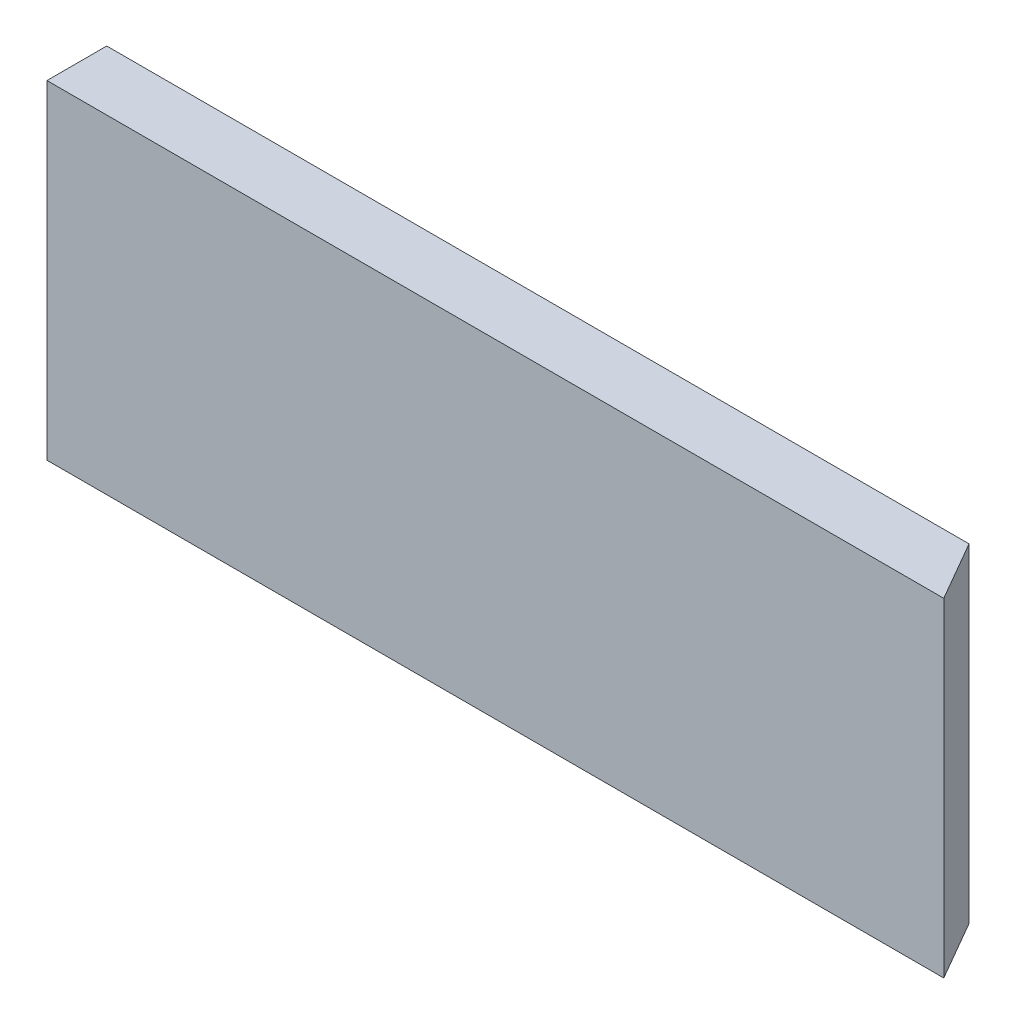
SolidWorks part; units mm, degrees
ref_plane "Front Plane" through (0, 0, 0) normal (0, 0, 1) x (1, 0, 0)
ref_plane "Top Plane" through (0, 0, 0) normal (0, 1, 0) x (1, 0, 0)
ref_plane "Right Plane" through (0, 0, 0) normal (1, 0, 0) x (0, 0, -1)
sketch "Sketch1" plane through (0, 0, 0) normal (0, 0, 1) x (1, 0, 0)
  line L1 (-47.625, -17.4625) -> (47.625, -17.4625)
  line L2 (-47.625, -17.4625) -> (-47.625, 17.4625)
  line L3 (-47.625, 17.4625) -> (47.625, 17.4625)
  line L4 (47.625, -17.4625) -> (47.625, 17.4625)
  line L5 (-47.625, -17.4625) -> (47.625, 17.4625) construction
  line L6 (-47.625, 17.4625) -> (47.625, -17.4625) construction
  point P0 (0, 0)
  dimension "D1" = 95.25
  dimension "D2" = 34.925
extrude "Boss-Extrude1" add sketch "Sketch1" along normal mid plane 6.35
sketch "Sketch2" plane through (0, 17.4625, 0) normal (0, 1, 0) x (1, 0, 0)
  line L0 (47.625, -3.175) -> (43.9588, 3.175)
  line L1 (47.625, 3.175) -> (-47.625, 3.175) construction
  line L2 (43.9588, 3.175) -> (47.625, 3.175)
  line L3 (47.625, -3.175) -> (47.625, 3.175) construction
  line L4 (47.625, 3.175) -> (47.625, -3.175)
  dimension "D1" = 30
extrude "Cut-Extrude1" cut sketch "Sketch2" against normal up to next
